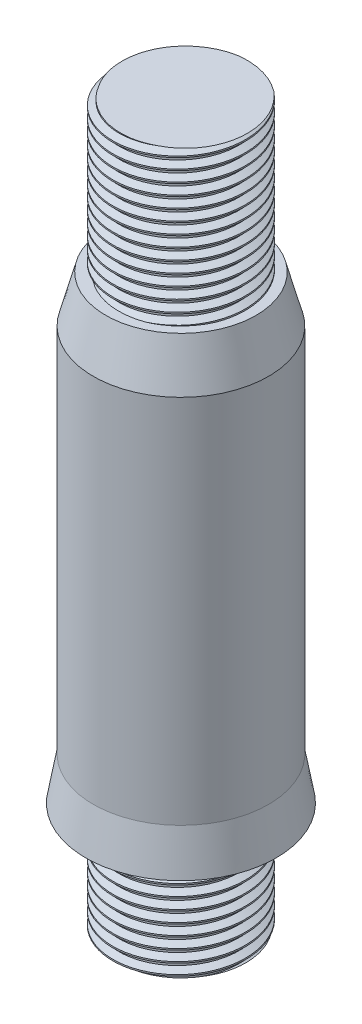
SolidWorks part; units mm, degrees
material "1.0401 (C15)"
ref_plane "Plano frontal" through (0, 0, 0) normal (0, 0, 1) x (1, 0, 0)
ref_plane "Plano superior" through (0, 0, 0) normal (0, 1, 0) x (1, 0, 0)
ref_plane "Plano direito" through (0, 0, 0) normal (1, 0, 0) x (0, 0, -1)
sketch "Esboço1" plane through (0, 0, 0) normal (0, 0, 1) x (1, 0, 0)
  line L0 (0, 0) -> (-11.6612, 0)
  line L12 (-11.6612, 0) -> (-11.6612, 55)
  line L13 (0, 0) -> (0, 81.1998)
  line L15 (-8, 81.1998) -> (-8, 61.1998)
  line L19 (-8, 81.1998) -> (0, 81.1998)
  line L20 (-8, 61.1998) -> (-10, 61.1998)
  line L21 (-10, 61.1998) -> (-11.6612, 55)
  line L22 (0, 0) -> (-12.6612, 0)
  line L23 (-12.6612, 0) -> (-11.6612, 5.6713)
  line L24 (0, 0) -> (0, -14.5)
  line L25 (0, -14.5) -> (-8, -14.5)
  line L26 (-8, -14.5) -> (-8, 0)
  dimension "D3" = 8
  dimension "D1" = 14.5
  dimension "D2" = 55
  dimension "D4" = 20
  dimension "D5" = 2
  dimension "D6" = 8
  dimension "D7" = 10
  dimension "D8" = 15
revolve "cilíndro" add sketch "Esboço1" angle 360 about L13 region at (-4, -7.25, 0) region at (-5.4621, 37.9101, 0) region at (-11.9946, 1.8904, 0)
thread "célula-de-carga" pitch 1.5 method extrude trim with start face yes trim with end face yes profile "Perfil da rosca1" start angle 0, offset 2.5, length 0, pitch 1.5, diameter 16
ref_plane "Plano1" through (-8, 83.6998, 0) normal (0, 0, 1) x (-1, 0, 0)
sketch "Perfil da rosca1" plane through (-8, 83.6998, 0) normal (0, 0, 1) x (-1, 0, 0)
  line L0 (0, 0) -> (0, 1.5) construction
  line L1 (0, 0) -> (0.8119, 0.4687)
  line L2 (0.8119, 0.4687) -> (0.8119, 0.6562)
  line L3 (0.8119, 0.6562) -> (0, 1.125)
  line L4 (0.8119, 0.5625) -> (0, 0.5625) construction
  line L11 (0, 0) -> (0, 1.125)
  point P2 (0, 0)
  dimension "Pitch" = 1.5
  dimension "Profile_Angle" = 60
  dimension "Profile_Land" = 0.1875
  dimension "Profile_Height" = 0.8119
thread "suporte" pitch 1.5 method extrude trim with start face yes trim with end face yes profile "Perfil da rosca2" start angle 0, offset 2.5, length 0, pitch 1.5, diameter 16
ref_plane "Plano2" through (8, -17, 0) normal (0, 0, 1) x (1, 0, 0)
sketch "Perfil da rosca2" plane through (8, -17, 0) normal (0, 0, 1) x (1, 0, 0)
  line L0 (0, 0) -> (0, 1.5) construction
  line L1 (0, 0) -> (0.8119, 0.4687)
  line L2 (0.8119, 0.4687) -> (0.8119, 0.6562)
  line L3 (0.8119, 0.6562) -> (0, 1.125)
  line L4 (0.8119, 0.5625) -> (0, 0.5625) construction
  line L11 (0, 0) -> (0, 1.125)
  point P2 (0, 0)
  dimension "Pitch" = 1.5
  dimension "Profile_Angle" = 60
  dimension "Profile_Land" = 0.1875
  dimension "Profile_Height" = 0.8119
